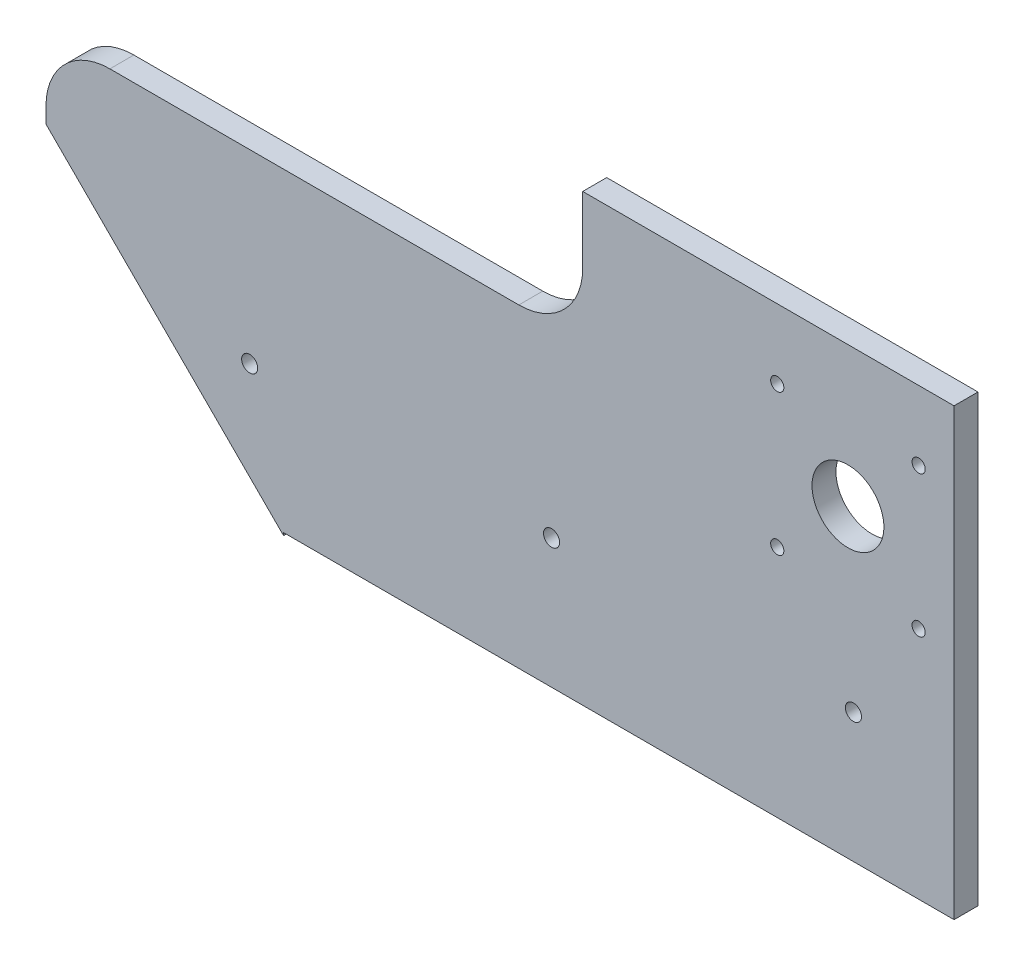
SolidWorks part; units mm, degrees
ref_plane "Front Plane" through (0, 0, 0) normal (0, 0, 1) x (1, 0, 0)
ref_plane "Top Plane" through (0, 0, 0) normal (0, 1, 0) x (1, 0, 0)
ref_plane "Right Plane" through (0, 0, 0) normal (1, 0, 0) x (0, 0, -1)
sketch "Sketch1" plane through (0, 0, 0) normal (0, 0, 1) x (1, 0, 0)
  line L0 (-138.2594, 48.9915) -> (32.2106, -121.4785)
  line L1 (32.2106, -121.4785) -> (222.7106, -121.4785)
  line L2 (-138.2594, 146.2068) -> (-138.2594, 48.9915)
  line L3 (-138.2594, 146.2068) -> (222.7106, 146.2068)
  line L4 (222.7106, -121.4785) -> (222.7106, 146.2068)
  circle A0 centre (180.538, 76.832) radius 14.2875
  circle A2 centre (180.538, 76.832) radius 69.85 construction
  circle A3 centre (180.538, 76.832) radius 318.7974 construction
  point P0 (0, 0)
  point P2 (180.538, 76.832)
  dimension "D4" = 198.3105
  dimension "D1" = 45
  dimension "D2" = 267.6854
  dimension "D5" = 245.11
extrude "Boss-Extrude1" add sketch "Sketch1" along normal blind 9.525
sketch "Sketch2" plane through (0, 0, 9.525) normal (0, 0, 1) x (1, 0, 0)
  line L0 (32.2106, -121.4785) -> (222.7106, -121.4785) construction
  line L1 (241.7606, -121.4785) -> (-43.8123, -121.4785)
  line L2 (241.7606, -121.4785) -> (241.7606, -44.3895)
  line L3 (241.7606, -44.3895) -> (-43.8123, -44.3895)
  line L4 (-43.8123, -121.4785) -> (-43.8123, -44.3895)
extrude "Cut-Extrude1" cut sketch "Sketch2" against normal through all contours L3 L4 L1 L2
sketch "Sketch4" plane through (0, 0, 9.525) normal (0, 0, 1) x (1, 0, 0)
  line L1 (-138.2594, 146.2068) -> (-138.2594, 48.9915) construction
  line L3 (-138.2594, 146.2068) -> (75.1006, 146.2068)
  line L4 (-138.2594, 146.2068) -> (-138.2594, 80.7415)
  line L5 (-138.2594, 80.7415) -> (75.1006, 80.7415)
  line L6 (75.1006, 146.2068) -> (75.1006, 80.7415)
extrude "Cut-Extrude2" cut sketch "Sketch4" against normal through all contours L5 L6 L3 L4
fillet "Fillet2" radius 25.4 2 edges at (-138.2594, 80.7415, 4.7625) (75.1006, 80.7415, 4.7625)
hole_wizard "Ø6.4 (6.4) Diameter Hole2" positions "Sketch15" profile "Sketch14" hole size "Ø6.4" standard "Lanco STD" end condition through all
sketch "Sketch15" plane through (0, 0, 0) normal (0, 0, -1) x (-1, 0, 0)
  line L2 (-222.7106, -44.3895) -> (-222.7106, 146.2068) construction
  point P3 (-182.7106, 7.0429)
  point P6 (-62.7106, 7.0429)
  point P9 (57.2894, 7.0429)
  dimension "D1" = 40
  dimension "D2" = 120
  dimension "D3" = 120
sketch "Sketch14" plane through (182.7106, 7.0429, 0) normal (1, 0, 0) x (0, 1, 0)
  line L0 (0, 0) -> (0, 9.525)
  line L1 (0, 9.525) -> (3.2, 9.525)
  line L2 (3.2, 9.525) -> (3.2, 0)
  line L5 (3.2, 0) -> (0, 0)
  line L11 (0, -6.35) -> (0, 107.95) construction
  dimension "Thru Hole Dia." = 6.4
  dimension "Thru Hole Depth" = 9.525
sketch "Sketch16" plane through (222.7106, 0, 0) normal (1, 0, 0) x (0, 0, -1)
  line L0 (0, -44.3895) -> (0, 146.2068) construction
  line L1 (-9.525, 146.2068) -> (0, 146.2068)
  line L2 (-9.525, 146.2068) -> (-9.525, 145.2215)
  line L3 (-9.525, 145.2215) -> (0, 145.2215)
  line L4 (0, 146.2068) -> (0, 145.2215)
extrude "Cut-Extrude3" cut sketch "Sketch16" against normal through all
sketch "Sketch17" plane through (0, 0, 0) normal (0, 0, -1) x (-1, 0, 0)
  line L0 (-222.7106, -44.3895) -> (-222.7106, 145.2215) construction
  line L1 (-75.1006, 145.2215) -> (-222.7106, 145.2215)
  line L2 (-75.1006, 145.2215) -> (-75.1006, 132.5215)
  line L3 (-75.1006, 132.5215) -> (-222.7106, 132.5215)
  line L4 (-222.7106, 145.2215) -> (-222.7106, 132.5215)
  dimension "D1" = 12.7
extrude "Cut-Extrude4" cut sketch "Sketch17" against normal through all
hole_wizard "Tap Drill for M6x0.75 Tap1" positions "Sketch19" profile "Sketch18" hole size "M6x0.75" standard "Lanco STD" end condition through all
sketch "Sketch19" plane through (0, 0, 9.525) normal (0, 0, 1) x (1, 0, 0)
  point P0 (208.638, 104.932)
  point P3 (152.438, 104.932)
  point P6 (152.438, 48.732)
  point P9 (208.638, 48.732)
sketch "Sketch18" plane through (208.638, 104.932, 9.525) normal (1, 0, 0) x (0, -1, 0)
  line L0 (0, 0) -> (0, 9.525)
  line L1 (0, 9.525) -> (2.625, 9.525)
  line L2 (2.625, 9.525) -> (2.625, 0)
  line L5 (2.625, 0) -> (0, 0)
  line L11 (0, -6.35) -> (0, 107.95) construction
  dimension "Thru Hole Dia." = 5.25
  dimension "Thru Hole Depth" = 9.525
